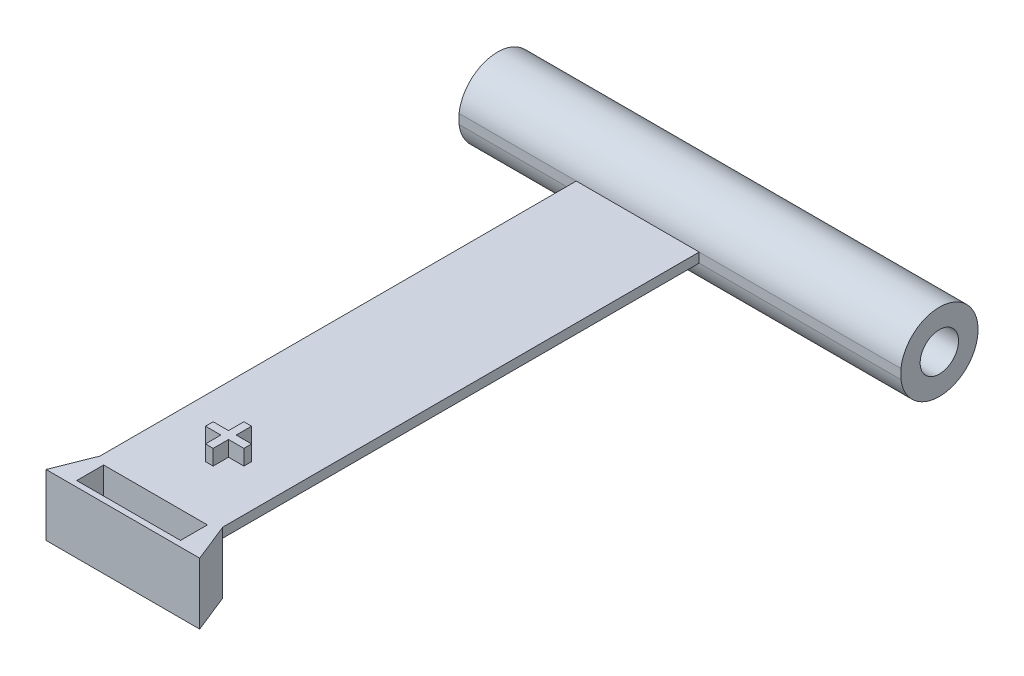
SolidWorks part; units mm, degrees
ref_plane "Front Plane" through (0, 0, 0) normal (0, 0, 1) x (1, 0, 0)
ref_plane "Top Plane" through (0, 0, 0) normal (0, 1, 0) x (1, 0, 0)
ref_plane "Right Plane" through (0, 0, 0) normal (1, 0, 0) x (0, 0, -1)
sketch "Sketch4" plane through (0, 0, 0) normal (0, 1, 0) x (1, 0, 0)
  line L0 (0, 0) -> (0, 20)
  line L1 (0, 0) -> (80, 0)
  line L2 (0, 0) -> (0, 20)
  line L3 (0, 20) -> (80, 20)
  line L4 (80, 0) -> (80, 20)
  line L5 (0, 20) -> (8, 20)
  line L6 (0, 0) -> (8, 20)
  line L7 (80, 20) -> (72, 20)
  line L8 (72, 20) -> (80, 0)
extrude "Boss-Extrude2" add sketch "Sketch4" along normal blind 32 contours L8 L3 L6 L1 region at (40, 0, -9.6296)
sketch "Sketch5" plane through (0, 32, 0) normal (0, 1, 0) x (1, 0, 0)
  line L0 (8, 20) -> (13, 20)
  line L2 (8, 20) -> (72, 20) construction
  line L3 (13, 20) -> (13, 17)
  line L4 (0, 0) -> (80, 0) construction
  line L5 (13, 0) -> (13, 3)
  line L6 (13, 17) -> (13, 3)
  line L7 (72, 20) -> (67, 20)
  line L8 (67, 20) -> (67, 3)
  line L9 (67, 3) -> (13, 3)
  line L10 (13, 17) -> (67, 17)
extrude "Cut-Extrude1" cut sketch "Sketch5" against normal blind 32 contours L10 L6 L9 L8 region at (40, 32, -10)
sketch "Sketch6" plane through (0, 0, -20) normal (0, 0, -1) x (-1, 0, 0)
  line L0 (-72, 32) -> (-72, 27)
  line L1 (-72, 32) -> (-72, 0) construction
  line L2 (-72, 27) -> (-8, 27)
  line L3 (-8, 32) -> (-8, 0) construction
  line L4 (-8, 27) -> (-8, 32)
  line L5 (-8, 32) -> (-72, 32)
extrude "Boss-Extrude3" add sketch "Sketch6" along normal blind 70
sketch "Sketch7" plane through (0, 32, 0) normal (0, 1, 0) x (1, 0, 0)
  line L0 (8, 55) -> (72, 55)
  line L1 (8, 90) -> (8, 20) construction
  line L2 (72, 90) -> (72, 20) construction
  line L3 (72, 55) -> (40, 55)
  line L4 (40, 55) -> (40, 65)
  line L5 (40, 65) -> (40, 55)
  line L6 (40, 55) -> (40, 45)
  line L7 (40, 45) -> (42, 45)
  line L8 (42, 45) -> (42, 65)
  line L9 (42, 65) -> (40, 65)
  line L10 (40, 45) -> (38, 45)
  line L11 (38, 45) -> (38, 65)
  line L12 (38, 65) -> (40, 65)
  line L13 (40, 55) -> (40, 57)
  line L14 (40, 57) -> (50, 57)
  line L15 (50, 57) -> (50, 53)
  line L16 (50, 53) -> (40, 53)
  line L17 (40, 53) -> (30, 53)
  line L18 (30, 53) -> (30, 57)
  line L19 (30, 57) -> (40, 57)
extrude "Boss-Extrude4" add sketch "Sketch7" along normal blind 8 contours L5 L14 L8 L9 | L11 L19 L5 L12 | L19 L11 L0 L4 | L14 L4 L0 L8 | L19 L18 L0 L11 | L18 L17 L11 L0 | L17 L6 L0 L11 | L16 L8 L0 L6 | L8 L16 L6 L7 | L6 L17 L11 L10 | L16 L15 L3 L8 | L15 L14 L8 L3 region at (34, 32, -56) region at (34, 32, -54) region at (39, 32, -56) region at (39, 32, -54) region at (41, 32, -56) region at (41, 32, -54) region at (39, 32, -49) region at (39, 32, -61) region at (46, 32, -56) region at (46, 32, -54) region at (41, 32, -61) region at (41, 32, -49)
sketch "Sketch8" plane through (0, 0, -90) normal (0, 0, -1) x (-1, 0, 0)
  line L0 (-8, 32) -> (-72, 32) construction
  line L1 (-72, 27) -> (-8, 27)
  line L2 (-72, 27) -> (-72, 32)
  line L3 (-72, 32) -> (-8, 32)
  line L4 (-8, 27) -> (-8, 32)
  line L5 (-8, 27) -> (-8, 32) construction
extrude "Boss-Extrude5" add sketch "Sketch8" along normal blind 178
sketch "Sketch13" plane through (72, 0, 0) normal (1, 0, 0) x (0, 0, -1)
  line L0 (268, 29.5) -> (288, 29.5)
  line L1 (268, 32) -> (268, 27) construction
  circle A0 centre (288, 29.5) radius 20.1556
  line M3 (268, 27) -> (268, 32)
extrude "Boss-Extrude7" add sketch "Sketch13" along normal blind 105 and the other way blind 125 contours A0 M3 region at (72, 29.5, -288.0082)
sketch "Sketch14" plane through (177, 0, 0) normal (1, 0, 0) x (0, 0, -1)
  line L0 (288, 49.6556) -> (288, 9.3444)
  arc A0 (268, 27) -> (268, 32) centre (288, 29.5) ccw construction
  circle A1 centre (288, 29.5) radius 10
extrude "Cut-Extrude4" cut sketch "Sketch14" against normal blind 264 contours L0 A1 | L0 A1 region at (177, 29.5, -292.2441) region at (177, 29.5, -283.7559)
